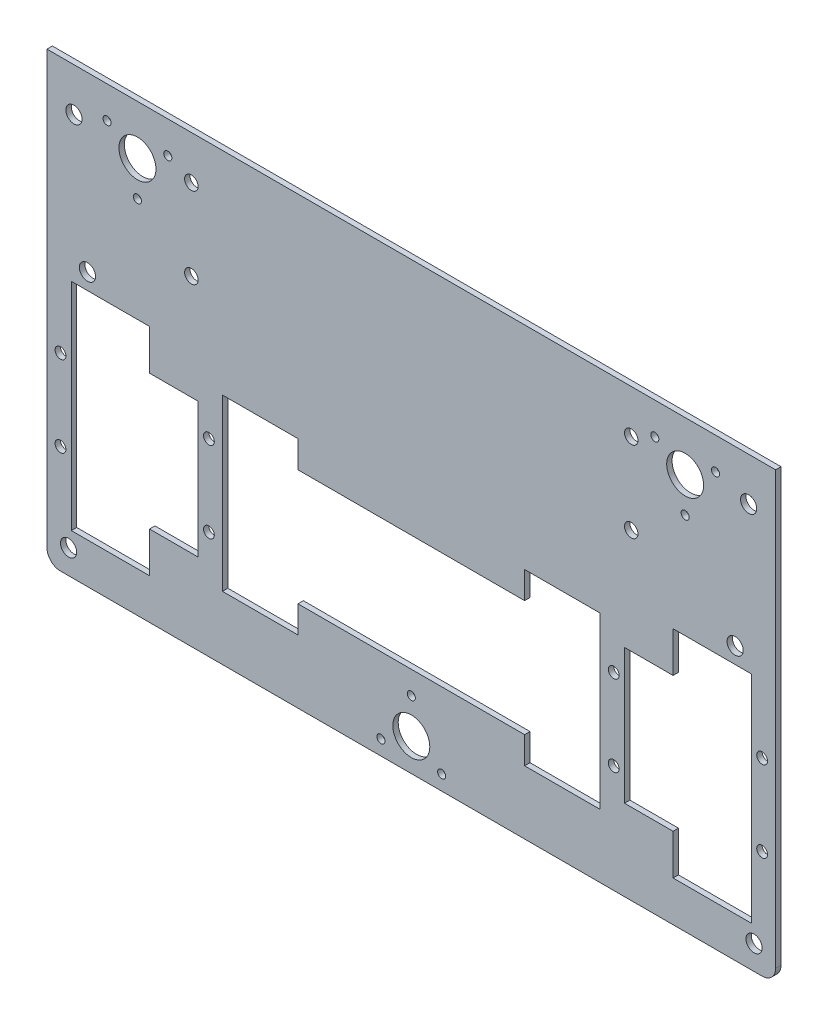
SolidWorks part; units mm, degrees
material "AISI 1020"
ref_plane "Front Plane" through (0, 0, 0) normal (0, 0, 1) x (1, 0, 0)
ref_plane "Top Plane" through (0, 0, 0) normal (0, 1, 0) x (1, 0, 0)
ref_plane "Right Plane" through (0, 0, 0) normal (1, 0, 0) x (0, 0, -1)
sketch "Sketch1" plane through (0, 0, 0) normal (0, 0, 1) x (1, 0, 0)
  line L0 (-135, -20.6351) -> (-135, -50)
  line L1 (-135, 50) -> (135, 50)
  line L2 (-135, 50) -> (-135, 40)
  line L3 (-135, -50) -> (135, -50)
  line L4 (135, 50) -> (135, 40)
  line L5 (-135, 50) -> (135, -50) construction
  line L6 (-135, -50) -> (135, 50) construction
  line L7 (-126, 40) -> (-97, 40)
  line L8 (0, -21.5) -> (0, -50) construction
  line L9 (-126, -40) -> (-97, -40)
  line L10 (-97, 40) -> (-97, 25)
  line L11 (-70, -31.5) -> (-42, -31.5)
  line L12 (-70, -31.5) -> (-70, 31.5)
  line L13 (-70, 31.5) -> (-42, 31.5)
  line L14 (-42, -31.5) -> (-42, -21.5)
  line L15 (-42, 21.5) -> (-42, 31.5)
  line L16 (-42, -21.5) -> (-4, -21.5)
  line L17 (42, 21.5) -> (42, 31.5)
  line L18 (-42, 21.5) -> (-4, 21.5)
  line L19 (135, -20.6351) -> (135, -50)
  line L20 (42, -31.5) -> (42, -21.5)
  line L21 (70, 31.5) -> (42, 31.5)
  line L22 (70, -31.5) -> (70, 31.5)
  line L23 (70, -31.5) -> (42, -31.5)
  line L24 (135, -20.6351) -> (135, 40)
  line L25 (4, -21.5) -> (-4, -21.5)
  line L26 (97, -40) -> (126, -40)
  line L27 (4, 21.5) -> (42, 21.5)
  line L28 (97, -40) -> (97, -25)
  line L29 (-4, -21.5) -> (-4, 21.5) construction
  line L30 (4, -21.5) -> (42, -21.5)
  line L31 (4, -21.5) -> (4, 21.5) construction
  line L32 (97, 40) -> (126, 40)
  line L33 (-135, 40) -> (-135, -20.6351)
  line L34 (126, -40) -> (126, 40)
  line L35 (-126, 40) -> (-126, -40)
  line L36 (97, 25) -> (79, 25)
  line L37 (-97, -25) -> (-97, -40)
  line L38 (97, -25) -> (79, -25)
  line L39 (79, 25) -> (79, -25)
  line L40 (4, 21.5) -> (-4, 21.5)
  line L41 (97, 25) -> (97, 40)
  line L42 (-97, 25) -> (-79, 25)
  line L44 (-97, -25) -> (-79, -25)
  line L45 (-79, 25) -> (-79, -25)
  circle A0 centre (-127, -46) radius 3
  circle A1 centre (-120, 46) radius 3
  circle A2 centre (120, 46) radius 3
  circle A3 centre (127, -46) radius 3
  point P0 (0, 0)
  point P14 (70, 0)
  point P51 (79, 0)
  point P55 (-79, 0)
  dimension "D10" = 6
  dimension "D13" = 6
  dimension "D15" = 4
  dimension "D1" = 270
  dimension "D2" = 100
  dimension "D3" = 18
  dimension "D4" = 10
  dimension "D5" = 80
  dimension "D6" = 63
  dimension "D7" = 28
  dimension "D8" = 42
  dimension "D9" = 43
  dimension "D11" = 15
  dimension "D12" = 6
  dimension "D14" = 8
  dimension "D16" = 10
  dimension "D17" = 8
  dimension "D18" = 9
  dimension "D19" = 29
  dimension "D20" = 29
  dimension "D21" = 80
  dimension "D22" = 10
  dimension "D23" = 9
  dimension "D24" = 50
  dimension "D25" = 18
  dimension "D26" = 50
extrude "Boss-Extrude1" add sketch "Sketch1" along normal blind 2
ref_plane "Plane1" through (0, 0, 0) normal (-1, 0, 0) x (0, 0, 1)
sketch "Sketch6" plane through (0, 0, 2) normal (0, 0, 1) x (1, 0, 0)
  line L0 (75, 110) -> (135, 110)
  line L1 (-135, 50) -> (135, 50)
  line L2 (-135, 50) -> (-135, 110)
  line L3 (-135, 110) -> (75, 110)
  line L4 (135, 50) -> (135, 110)
  line L5 (-126, 0) -> (-79, 0) construction
  line L9 (-126, 40) -> (-126, -40) construction
  line L11 (-135, -50) -> (135, -50)
  line L12 (-135, -50) -> (-135, -55)
  line L13 (-130, -60) -> (130, -60)
  line L14 (135, -50) -> (135, -55)
  line L19 (-79, -25) -> (-79, 25) construction
  arc A0 (130, -60) -> (135, -55) centre (130, -55) ccw
  circle A1 centre (-125, 94) radius 3
  circle A4 centre (125, 94) radius 3
  arc A5 (-135, -55) -> (-130, -60) centre (-130, -55) ccw
  point P12 (135, 110)
  point P15 (-135, 110)
  point P28 (135, -60)
  point P31 (-135, -60)
  dimension "D3" = 10
  dimension "D4" = 6
  dimension "D5" = 10
  dimension "D6" = 10
  dimension "D7" = 16
  dimension "D12" = 6
  dimension "D14" = 16
  dimension "D9" = 5
  dimension "D1" = 270
  dimension "D2" = 60
  dimension "D13" = 270
extrude "Boss-Extrude2" add sketch "Sketch6" against normal blind 2 separate body
combine bodies "Combine1" operation type add bodies to combine 108 101
combine bodies "Combine2" operation type add bodies to combine 107 114
sketch "Sketch7" plane through (0, 0, 2) normal (0, 0, 1) x (1, 0, 0)
  line L0 (135, -55) -> (135, 110) construction
  line L1 (75, -110) -> (125, -110) construction
  line L2 (-75, -95) -> (75, -95) construction
  line L3 (-126, 0) -> (-79, 0) construction
  line L4 (-126, 40) -> (-126, -40) construction
  line L5 (-135, 110) -> (-135, -55) construction
  line L6 (-79, -25) -> (-79, 25) construction
  line L7 (135, 110) -> (-135, 110) construction
  line L8 (0, 110) -> (0, 19.5645) construction
  line L10 (-130, -60) -> (130, -60) construction
  line L12 (135, 110) -> (-135, 110) construction
  circle A0 centre (11.25, -49.4952) radius 1.5
  circle A1 centre (-11.25, -49.4952) radius 1.5
  circle A2 centre (0, -30.0096) radius 1.5
  circle A3 centre (0, -43) radius 15.6
  circle A4 centre (90.2347, 98.1802) radius 1.5
  circle A5 centre (0, -43) radius 6.85
  circle A6 centre (112.7347, 98.1802) radius 1.5
  circle A7 centre (101.4847, 78.6947) radius 1.5
  circle A8 centre (101.4847, 91.6851) radius 6.85
  circle A13 centre (-101.4847, 91.6851) radius 6.85
  circle A14 centre (-101.4847, 78.6947) radius 1.5
  circle A15 centre (-112.7347, 98.1802) radius 1.5
  circle A16 centre (-90.2347, 98.1802) radius 1.5
  point P19 (0, -95)
  dimension "D1" = 13.7
  dimension "D2" = 31.2
  dimension "D3" = 3
  dimension "D5" = 11.25
  dimension "D6" = 19.4856
  dimension "D7" = 22.5
  dimension "D8" = 12.9904
  dimension "D9" = 17
  dimension "D10" = 22.2653
  dimension "D12" = 33.5153
  dimension "D18" = 13.7
  dimension "D4" = 10
  dimension "D11" = 220
  dimension "D13" = 44.7653
  dimension "D14" = 11.8198
  dimension "D15" = 18.3149
  dimension "D16" = 31.3053
extrude "Cut-Extrude4" cut sketch "Sketch7" against normal blind 10 contours A5 | A2 | A13 | A16 | A15 | A8 | A1 | A0 | A14 | A7 | A4 | A6 region at (0, -30.0096, 2) region at (0, -43, 2) region at (101.4847, 91.6851, 2) region at (-101.4847, 91.6851, 2) region at (-112.7347, 98.1802, 2) region at (-90.2347, 98.1802, 2)
sketch "Sketch8" plane through (0, 0, 0) normal (0, 0, -1) x (-1, 0, 0)
  circle A0 centre (-130, -15) radius 2 construction
  circle A1 centre (-130, 15) radius 2 construction
  circle A2 centre (-75, -15) radius 2 construction
  circle A3 centre (-75, 15) radius 2 construction
  circle A4 centre (75, -15) radius 2 construction
  circle A5 centre (75, 15) radius 2 construction
  circle A6 centre (130, -15) radius 2 construction
  circle A7 centre (130, 15) radius 2 construction
  circle A8 centre (-130, -15) radius 2
  circle A9 centre (-130, 15) radius 2
  circle A10 centre (-75, -15) radius 2
  circle A11 centre (-75, 15) radius 2
  circle A12 centre (75, -15) radius 2
  circle A13 centre (75, 15) radius 2
  circle A14 centre (130, -15) radius 2
  circle A15 centre (130, 15) radius 2
extrude "Cut-Extrude5" cut sketch "Sketch8" against normal through all
sketch "Sketch9" plane through (0, 0, 0) normal (0, 0, -1) x (-1, 0, 0)
  circle A0 centre (81.5, 93.8981) radius 2.5 construction
  circle A1 centre (81.5, 63.8981) radius 2.5 construction
  circle A2 centre (-81.5, 93.8981) radius 2.5 construction
  circle A3 centre (-81.5, 63.8981) radius 2.5 construction
  circle A4 centre (81.5, 93.8981) radius 2.5
  circle A5 centre (81.5, 63.8981) radius 2.5
  circle A6 centre (-81.5, 93.8981) radius 2.5
  circle A7 centre (-81.5, 63.8981) radius 2.5
extrude "Cut-Extrude6" cut sketch "Sketch9" against normal blind 10
sketch "Sketch10" plane through (0, 0, 2) normal (0, 0, 1) x (1, 0, 0)
  line L0 (-130, -60) -> (130, -60) construction
  line L1 (-130, -60) -> (130, -60)
  line L2 (135, -55) -> (-135, -55)
  arc A0 (130, -60) -> (135, -55) centre (130, -55) ccw construction
  arc A1 (-135, -55) -> (-130, -60) centre (-130, -55) ccw construction
  arc A2 (130, -60) -> (135, -55) centre (130, -55) ccw
  arc A3 (-135, -55) -> (-130, -60) centre (-130, -55) ccw
extrude "Cut-Extrude7" cut sketch "Sketch10" against normal blind 10
fillet "Fillet1" radius 5 2 edges at (135, -55, 1) (-135, -55, 1)
